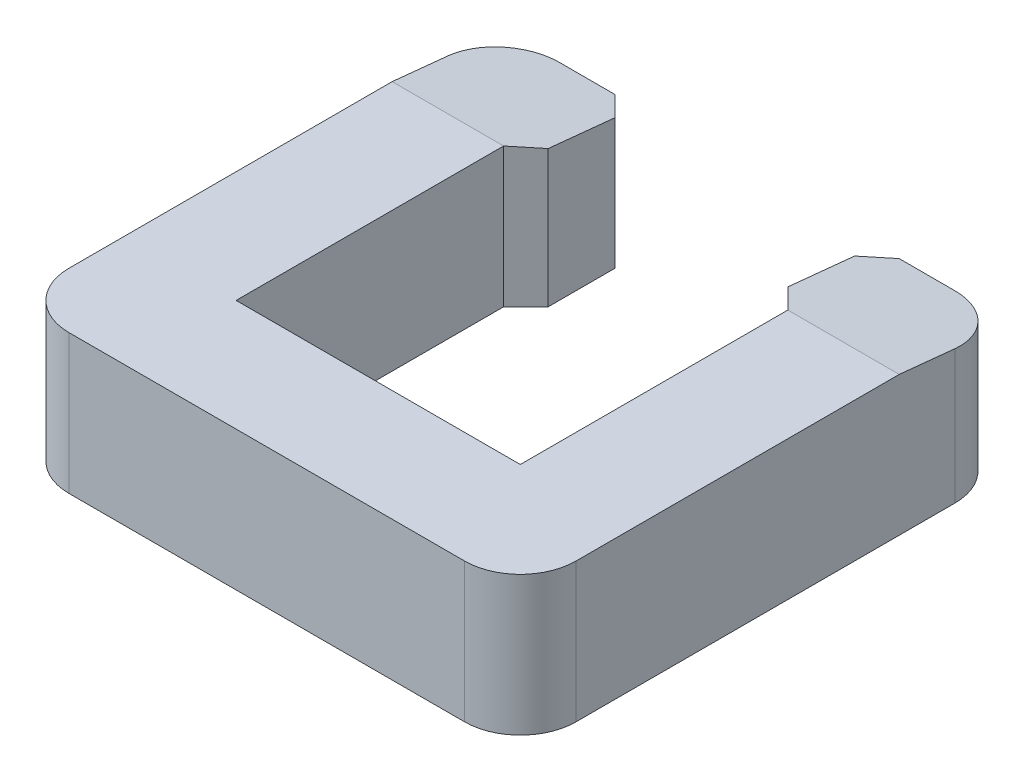
SolidWorks part; units mm, degrees
ref_plane "Front Plane" through (0, 0, 0) normal (0, 0, 1) x (1, 0, 0)
ref_plane "Top Plane" through (0, 0, 0) normal (0, 1, 0) x (1, 0, 0)
ref_plane "Right Plane" through (0, 0, 0) normal (1, 0, 0) x (0, 0, -1)
sketch "Sketch1" plane through (0, 0, 0) normal (0, 1, 0) x (1, 0, 0)
  line L0 (-5.7785, 5.588) -> (-5.7785, -5.588)
  line L1 (-3.2385, 3.048) -> (3.2385, 3.048) construction
  line L2 (-3.2385, 3.048) -> (-3.2385, -3.048)
  line L3 (-3.2385, -3.048) -> (3.2385, -3.048)
  line L4 (3.2385, 3.048) -> (3.2385, -3.048)
  line L5 (-5.7785, -5.588) -> (5.7785, -5.588)
  line L6 (5.7785, 5.588) -> (5.7785, -5.588)
  line L7 (-5.7785, 5.588) -> (-3.2385, 5.588)
  line L8 (-3.2385, 5.588) -> (-3.2385, 3.048) construction
  line L9 (3.2385, 5.588) -> (3.2385, 3.048) construction
  line L10 (3.2385, 5.588) -> (5.7785, 5.588)
  line L11 (-3.2385, 5.588) -> (-2.7305, 5.08)
  line L12 (-5.7785, 5.588) -> (5.7785, 5.588) construction
  line L13 (-2.7305, 5.08) -> (-2.7305, 3.556)
  line L14 (-2.7305, 3.556) -> (-3.2385, 3.048)
  line L15 (0, 3.048) -> (0, 5.54) construction
  line L16 (2.7305, 3.556) -> (3.2385, 3.048)
  line L17 (3.2385, 5.588) -> (2.7305, 5.08)
  line L18 (2.7305, 5.08) -> (2.7305, 3.556)
  point P4 (0, 3.048)
  point P6 (-3.2385, 0)
  dimension "D1" = 6.477
  dimension "D2" = 6.096
  dimension "D4" = 1.524
  dimension "D5" = 0.508
  dimension "D6" = 0.508
  dimension "D3" = 2.54
extrude "Boss-Extrude1" add sketch "Sketch1" along normal blind 3.175
fillet "Fillet1" radius 1.27 4 edges at (-5.7785, 1.5875, -5.588) (5.7785, 1.5875, -5.588) (5.7785, 1.5875, 5.588) (-5.7785, 1.5875, 5.588)
sketch "Sketch2" plane through (5.7785, 0, 0) normal (1, 0, 0) x (0, 0, -1)
  line L0 (5.588, 3.175) -> (3.048, 3.175)
  line L1 (-4.318, 3.175) -> (4.318, 3.175) construction
  line L2 (3.048, 3.175) -> (5.588, 2.921)
  line L3 (5.588, 3.175) -> (5.588, 0) construction
  line L4 (5.588, 2.921) -> (5.588, 3.175)
  dimension "D1" = 2.54
  dimension "D2" = 0.254
extrude "Cut-Extrude1" cut sketch "Sketch2" against normal through all
